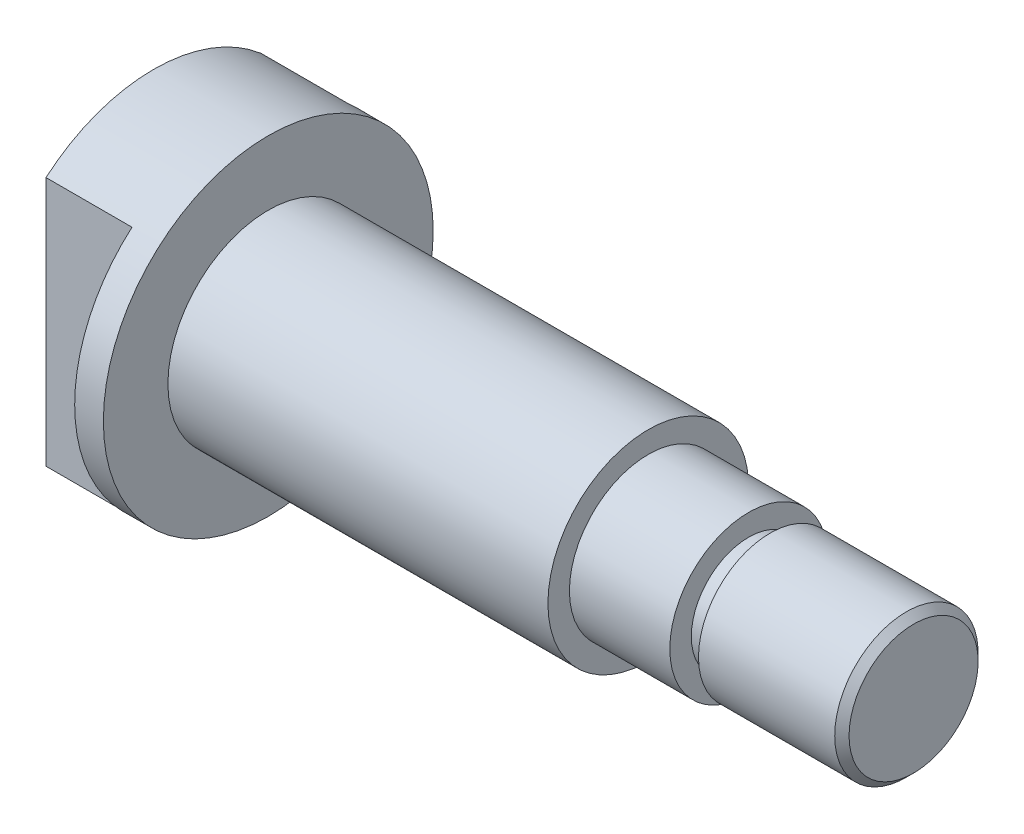
SolidWorks part; units mm, degrees
material "Alloy Steel (SS)"
ref_plane "Front Plane" through (0, 0, 0) normal (0, 0, 1) x (1, 0, 0)
ref_plane "Top Plane" through (0, 0, 0) normal (0, 1, 0) x (1, 0, 0)
ref_plane "Right Plane" through (0, 0, 0) normal (1, 0, 0) x (0, 0, -1)
sketch "Sketch1" plane through (0, 0, 0) normal (0, 0, 1) x (1, 0, 0)
  line L0 (0, 0) -> (124.509, 0) construction
  line L1 (0, 0) -> (0, 23)
  line L2 (0, 23) -> (16, 23)
  line L3 (16, 23) -> (16, 14)
  line L4 (16, 14) -> (69, 14)
  line L5 (69, 14) -> (69, 11)
  line L6 (69, 11) -> (83, 11)
  line L7 (83, 11) -> (83, 8)
  line L8 (83, 8) -> (86, 8)
  line L9 (86, 8) -> (86, 10)
  line L10 (86, 10) -> (106, 10)
  line L11 (106, 10) -> (106, 0)
  line L12 (106, 0) -> (0, 0)
  dimension "D1" = 106
  dimension "D2" = 16
  dimension "D3" = 53
  dimension "D4" = 14
  dimension "D5" = 3
  dimension "D6" = 20
  dimension "D7" = 22
  dimension "D8" = 28
  dimension "D9" = 46
  dimension "D10" = 16
revolve "Revolve1" add sketch "Sketch1" angle 360 about L0
cosmetic thread "Cosmetic Thread1" parameters "D2"=17.252
chamfer "Chamfer1" distance 1 angle 45 1 edges at (106, 0, 10)
sketch "Sketch2" plane through (0, 0, 0) normal (-1, 0, 0) x (0, 0, 1)
  line L0 (-15, 17.4356) -> (-15, -17.4356)
  line L1 (15, 17.4356) -> (15, -17.4356)
  circle A0 centre (0, 0) radius 23 construction
  arc A1 (-15, 17.4356) -> (-15, -17.4356) centre (0, 0) ccw
  arc A2 (15, 17.4356) -> (-15, 17.4356) centre (0, 0) ccw construction
  arc A3 (-15, -17.4356) -> (15, -17.4356) centre (0, 0) ccw construction
  arc A4 (15, -17.4356) -> (15, 17.4356) centre (0, 0) ccw
  dimension "D1" = 30
extrude "Cut-Extrude1" cut sketch "Sketch2" against normal blind 12
ref_axis "Axis1" through (110.7054, 0, 0) along (-1, 0, 0)
